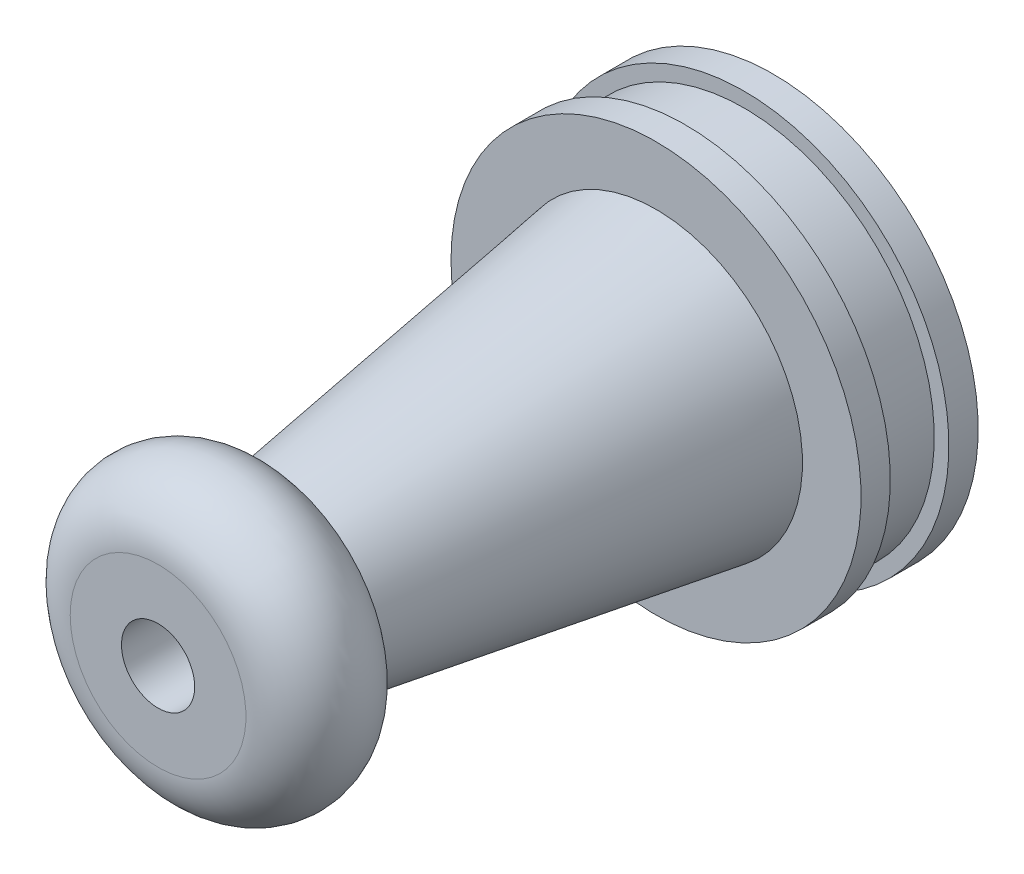
SolidWorks part; units mm, degrees
ref_plane "Front Plane" through (0, 0, 0) normal (0, 0, 1) x (1, 0, 0)
ref_plane "Top Plane" through (0, 0, 0) normal (0, 1, 0) x (1, 0, 0)
ref_plane "Right Plane" through (0, 0, 0) normal (1, 0, 0) x (0, 0, -1)
sketch "Sketch3" plane through (0, 0, 0) normal (0, 1, 0) x (1, 0, 0)
  line L0 (0, 50.3098) -> (0, -50.3098) construction
  line L1 (0, 10.16) -> (0, -10.16)
  line L2 (0, 10.16) -> (15.24, 10.16)
  line L3 (0, -10.16) -> (15.24, -10.16)
  arc A0 (15.24, 10.16) -> (15.24, -10.16) centre (15.24, 0) cw
  point P4 (0, 0)
  point P7 (0, 0)
  point P10 (0, 0)
  dimension "D1" = 10.16
  dimension "D2" = 15.24
revolve "Revolve1" add sketch "Sketch3" angle 360 about L0
sketch "Sketch4" plane through (0, 0, 10.16) normal (0, 0, 1) x (1, 0, 0)
  circle A0 centre (0, 0) radius 6.35
  dimension "D1" = 12.7
sketch "Sketch5" plane through (0, 0, -10.16) normal (0, 0, -1) x (-1, 0, 0)
  circle A0 centre (0, 0) radius 15.24
  dimension "D1" = 30.48
ref_plane "Plane1" through (0, 0, -76.2) normal (0, 0, 1) x (1, 0, 0)
sketch "Sketch6" plane through (0, 0, -76.2) normal (0, 0, 1) x (1, 0, 0)
  circle A0 centre (0, 0) radius 25.4
  dimension "D1" = 50.8
loft "Loft1" add profiles "Sketch5", "Sketch6" connector at (-10.516, 11.0305, -10.16) connector at (-15.7938, 19.8926, -76.2)
sketch "Sketch7" plane through (0, 0, -76.2) normal (0, 0, -1) x (-1, 0, 0)
  circle A0 centre (0, 0) radius 35.56
  dimension "D1" = 71.12
extrude "Boss-Extrude1" add sketch "Sketch7" along normal blind 20.32
ref_plane "Plane2" through (0, 0, -91.44) normal (0, 0, -1) x (-1, 0, 0)
sketch "Sketch8" plane through (0, 0, -91.44) normal (0, 0, -1) x (-1, 0, 0)
  circle A0 centre (0, 0) radius 33.02
  circle A1 centre (0, 0) radius 35.56
  dimension "D1" = 66.04
  dimension "D2" = 71.12
extrude "Cut-Extrude4" cut sketch "Sketch8" against normal blind 10.16
sketch "Sketch9" plane through (0, 0, -96.52) normal (0, 0, -1) x (-1, 0, 0)
  circle A0 centre (0, 0) radius 30.48
  dimension "D1" = 60.96
extrude "Cut-Extrude5" cut sketch "Sketch9" against normal blind 17.78
extrude "Cut-Extrude6" cut sketch "Sketch4" against normal through all
fillet "Fillet1" radius 2.54 1 edges at (-30.48, 0, -78.74)
sketch "Sketch10" plane through (0, 0, -78.74) normal (0, 0, -1) x (-1, 0, 0)
  circle A0 centre (0, 0) radius 6.35
  dimension "D1" = 12.7
sketch "Sketch12" plane through (0, 0, -78.74) normal (0, 0, -1) x (-1, 0, 0)
  circle A0 centre (0, 0) radius 30.48
  dimension "D1" = 60.96
extrude "Boss-Extrude2" add sketch "Sketch12" along normal blind 17.78
sketch "Sketch13" plane through (0, 0, -96.52) normal (0, 0, -1) x (-1, 0, 0)
  circle A0 centre (0, 0) radius 25.4
  dimension "D1" = 50.8
loft "Cut-Loft2" cut profiles "Sketch13", "Sketch10" connector at (19.6319, 16.1167, -96.52) connector at (-6.35, 0, -78.74)
sketch "Sketch14" plane through (0, 0, 10.16) normal (0, 0, 1) x (1, 0, 0)
  circle A0 centre (0, 0) radius 6.35
  dimension "D1" = 12.7
extrude "Cut-Extrude7" cut sketch "Sketch14" against normal through all
